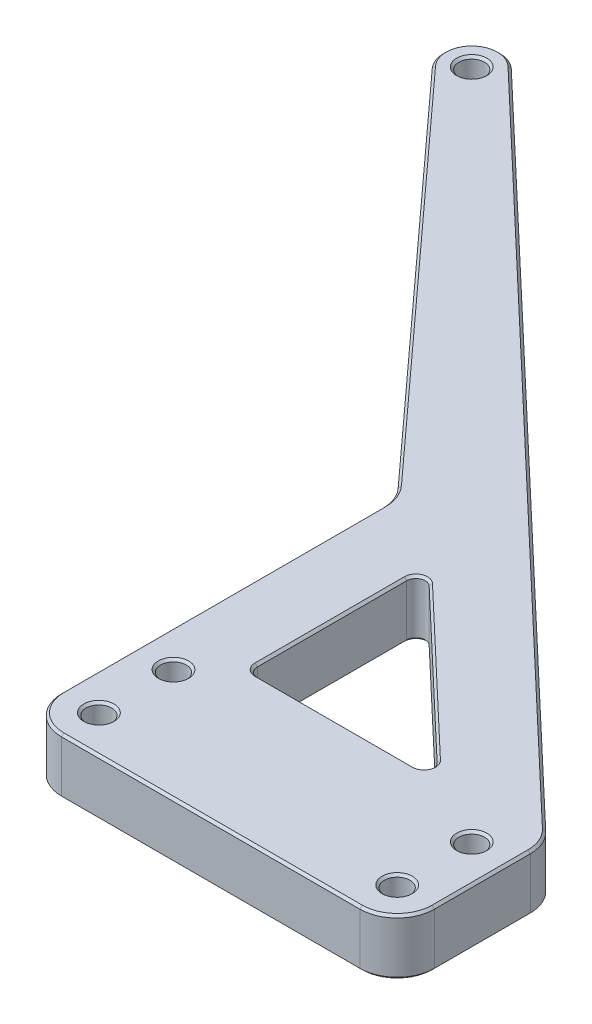
SolidWorks part; units mm, degrees
ref_plane "Front Plane" through (0, 0, 0) normal (0, 0, 1) x (1, 0, 0)
ref_plane "Top Plane" through (0, 0, 0) normal (0, 1, 0) x (1, 0, 0)
ref_plane "Right Plane" through (0, 0, 0) normal (1, 0, 0) x (0, 0, -1)
sketch "Sketch1" plane through (0, 0, 0) normal (0, 1, 0) x (1, 0, 0)
  line L6 (50.8, -6.35) -> (0, -6.35)
  line L7 (-6.35, 0) -> (-6.35, 54.6925)
  line L8 (-8.0044, 58.9673) -> (-67.0217, 123.7939)
  line L9 (-60.2214, 130.4543) -> (55.1715, 20.9279)
  line L10 (57.15, 16.3222) -> (57.15, 0)
  circle A0 centre (0, 0) radius 2.1828
  circle A3 centre (50.8, 12.7) radius 2.1828
  circle A4 centre (-63.5, 127) radius 2.1828
  arc A11 (-60.2214, 130.4543) -> (-67.0217, 123.7939) centre (-63.5, 127) ccw
  arc A12 (50.8, -6.35) -> (57.15, 0) centre (50.8, 0) ccw
  arc A13 (0, -6.35) -> (-6.35, 0) centre (0, 0) cw
  arc A14 (55.1715, 20.9279) -> (57.15, 16.3222) centre (50.8, 16.3222) cw
  arc A15 (-6.35, 54.6925) -> (-8.0044, 58.9673) centre (-12.7, 54.6925) ccw
  circle A16 centre (0, 12.7) radius 2.1828
  circle A17 centre (50.8, 0) radius 2.1828
  point P16 (57.15, -6.35)
  point P19 (-6.35, -6.35)
  point P22 (57.15, 19.05)
  point P25 (-6.35, 57.15)
  point P29 (0, 0)
  point P30 (0, 0)
  point P31 (0, 0)
  point P32 (0, 0)
  dimension "D5" = 4.3656
  dimension "D6" = 9.525
  dimension "D7" = 6.35
  dimension "D8" = 4.3656
  dimension "D11" = 4.3656
  dimension "D12" = 63.5
  dimension "D15" = 6.35
  dimension "D16" = 4.3656
  dimension "D17" = 4.3656
  dimension "D2" = 6.35
  dimension "D3" = 50.8
  dimension "D4" = 12.7
  dimension "D9" = 127
  dimension "D10" = 63.5
  dimension "D13" = 25.4
  dimension "D14" = 63.5
extrude "Boss-Extrude1" add sketch "Sketch1" along normal blind 9.525
sketch "Sketch3" plane through (0, 0, 0) normal (0, 1, 0) x (1, 0, 0)
  line L0 (9.0304, 47.2133) -> (35.8166, 21.7889)
  line L3 (55.1715, 20.9279) -> (-60.2214, 130.4543) construction
  line L4 (6.35, 46.0619) -> (6.35, 20.6375)
  line L5 (7.9375, 19.05) -> (34.7237, 19.05)
  line L6 (0, -6.35) -> (50.8, -6.35) construction
  line L7 (-6.35, 54.6925) -> (-6.35, 0) construction
  arc A0 (35.8166, 21.7889) -> (34.7237, 19.05) centre (34.7237, 20.6375) cw
  arc A1 (6.35, 20.6375) -> (7.9375, 19.05) centre (7.9375, 20.6375) ccw
  arc A2 (9.0304, 47.2133) -> (6.35, 46.0619) centre (7.9375, 46.0619) ccw
  dimension "D4" = 1.5875
  dimension "D1" = 12.7
  dimension "D2" = 12.7
  dimension "D3" = 25.4
extrude "Cut-Extrude2" cut sketch "Sketch3" along normal through all both and the other way through all
chamfer "Chamfer1" distance 0.3969 angle 45 42 edges at (-63.5, 9.525, -124.8172) (0, 9.525, 2.1828) (25.4, 9.525, 6.35) (-4.4901, 9.525, 4.4901) (-6.35, 9.525, -27.3462) (-6.778, 9.525, -56.9843) (-37.5131, 9.525, -91.3806) (-66.8324, 9.525, -130.4024) (-2.5249, 9.525, -75.6911) (56.6345, 9.525, -18.8285) (57.15, 9.525, -8.1611) (55.2901, 9.525, 4.4901) (50.8, 9.525, -10.5172) (21.3306, 0, -19.05) (6.815, 0, -19.515) (6.35, 0, -33.3497) (7.3109, 0, -47.5205) (22.4235, 0, -34.5011) (36.1982, 0, -20.0492) (57.15, 0, -8.1611) (56.6345, 0, -18.8285) (-2.5249, 0, -75.6911) (-66.8324, 0, -130.4024) (-37.5131, 0, -91.3806) (-6.778, 0, -56.9843) (-6.35, 0, -27.3462) (-4.4901, 0, 4.4901) (25.4, 0, 6.35) (55.2901, 0, 4.4901) (0, 0, 2.1828) (50.8, 0, -10.5172) (-63.5, 0, -124.8172) (7.3109, 9.525, -47.5205) (6.35, 9.525, -33.3497) (6.815, 9.525, -19.515) (21.3306, 9.525, -19.05) (36.1982, 9.525, -20.0492) (22.4235, 9.525, -34.5011) (50.8, 9.525, 2.1828) (0, 9.525, -10.5172) (0, 0, -10.5172) (50.8, 0, 2.1828)
